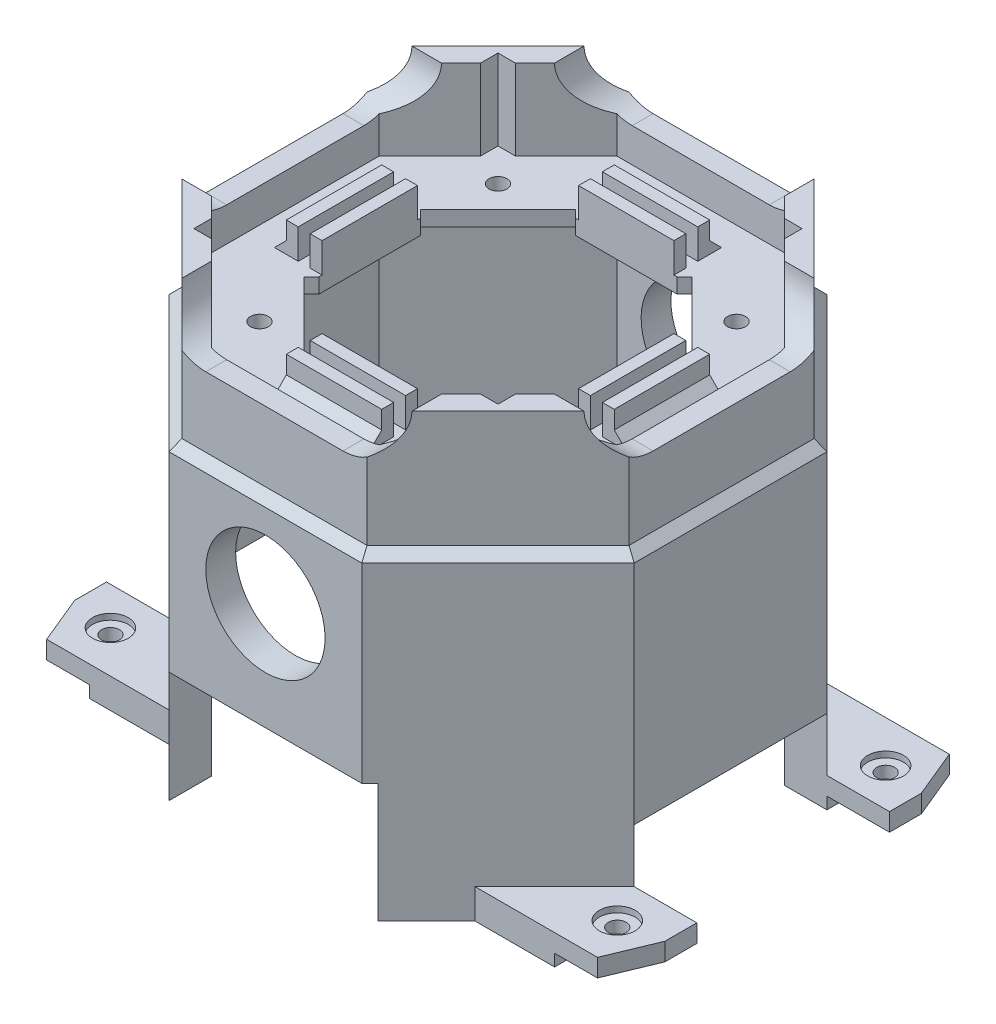
SolidWorks part; units mm, degrees
ref_plane "Front Plane" through (0, 0, 0) normal (0, 0, 1) x (1, 0, 0)
ref_plane "Top Plane" through (0, 0, 0) normal (0, 1, 0) x (1, 0, 0)
ref_plane "Right Plane" through (0, 0, 0) normal (1, 0, 0) x (0, 0, -1)
sketch "Sketch1" plane through (0, 0, 0) normal (0, 1, 0) x (1, 0, 0)
  line L1 (15.533, 37.5) -> (-15.533, 37.5)
  line L2 (-15.533, 37.5) -> (-37.5, 15.533)
  line L3 (-37.5, 15.533) -> (-37.5, -15.533)
  line L4 (-37.5, -15.533) -> (-15.533, -37.5)
  line L5 (-15.533, -37.5) -> (15.533, -37.5)
  line L6 (15.533, -37.5) -> (37.5, -15.533)
  line L7 (37.5, -15.533) -> (37.5, 15.533)
  line L8 (37.5, 15.533) -> (15.533, 37.5)
  circle A0 centre (0, 0) radius 37.5 construction
  dimension "D1" = 75
extrude "Boss-Extrude1" add sketch "Sketch1" along normal blind 40
sketch "Sketch7" plane through (0, 0, 0) normal (0, -1, 0) x (1, 0, 0)
  line L0 (-15.533, 37.5) -> (15.533, 37.5) construction
  line L1 (39, 16.1543) -> (16.1543, 39)
  line L2 (16.1543, 39) -> (-16.1543, 39)
  line L3 (-16.1543, 39) -> (-39, 16.1543)
  line L4 (-39, 16.1543) -> (-39, -16.1543)
  line L5 (-39, -16.1543) -> (-16.1543, -39)
  line L6 (-16.1543, -39) -> (16.1543, -39)
  line L7 (16.1543, -39) -> (39, -16.1543)
  line L8 (39, -16.1543) -> (39, 16.1543)
  circle A0 centre (0, 0) radius 39 construction
  dimension "76" = 78
extrude "Boss-Extrude4" add sketch "Sketch7" along normal blind 55
sketch "Sketch18" plane through (0, 40, 0) normal (0, 1, 0) x (1, 0, 0)
  line L0 (-39, -16.1543) -> (-39, 16.1543) construction
  line L2 (-39, 7.5) -> (-39, -7.5)
  line L12 (-39, 7.5) -> (-33, 7.5)
  line L14 (-33, 7.5) -> (-33, -7.5)
  line L15 (-33, -7.5) -> (-39, -7.5)
  line L16 (0, -55) -> (0, 55) construction
  line L17 (33, 7.5) -> (33, -7.5)
  line L18 (39, 7.5) -> (33, 7.5)
  line L19 (39, 7.5) -> (39, -7.5)
  line L20 (33, -7.5) -> (39, -7.5)
  point P1 (-33, 0)
  dimension "D1" = 15
  dimension "D2" = 6
  dimension "D3" = 6
sketch "Sketch3" plane through (0, 0, 37.5) normal (0, 0, 1) x (1, 0, 0)
  line L0 (-11.5, 18) -> (11.5, 18) construction
  line L1 (-11.5, 25.8) -> (11.5, 25.8)
  line L2 (-11.5, 10.2) -> (11.5, 10.2)
  line L4 (-15.533, 40) -> (15.533, 40) construction
  arc A0 (-11.5, 25.8) -> (-11.5, 10.2) centre (-11.5, 18) ccw
  arc A1 (11.5, 10.2) -> (11.5, 25.8) centre (11.5, 18) ccw
  point P2 (0, 18)
  dimension "D1" = 7.8
  dimension "D2" = 23
  dimension "D3" = 22
extrude "Cut-Extrude1" cut sketch "Sketch3" against normal up to surface (75 mm away) up to face at (0, 20, -37.5)
sketch "Sketch4" plane through (-37.5, 0, 0) normal (-1, 0, 0) x (0, 0, 1)
  line L0 (-11.5, 18) -> (11.5, 18) construction
  line L1 (-11.5, 25.8) -> (11.5, 25.8)
  line L2 (-11.5, 10.2) -> (11.5, 10.2)
  line L4 (-15.533, 40) -> (15.533, 40) construction
  arc A0 (-11.5, 25.8) -> (-11.5, 10.2) centre (-11.5, 18) ccw
  arc A1 (11.5, 10.2) -> (11.5, 25.8) centre (11.5, 18) ccw
  point P2 (0, 18)
  dimension "D1" = 7.8
  dimension "D2" = 22
  dimension "D3" = 23
extrude "Cut-Extrude2" cut sketch "Sketch4" against normal up to surface and the other way up to surface up to face at (39, -27.5, 0) other way up to face at (-39, -27.5, 0)
chamfer "Chamfer5" distance 3 angle 45 8 edges at (-39, 0, 0) (-27.5772, 0, -27.5772) (0, 0, -39) (27.5772, 0, -27.5772) (39, 0, 0) (27.5772, 0, 27.5772) (0, 0, 39) (-27.5772, 0, 27.5772)
shell "Shell1" [suppressed] thickness 2
sketch "Sketch11" plane through (0, 0, -39) normal (0, 0, 1) x (1, 0, 0)
  line L1 (16.1543, -55) -> (-16.1543, -55) construction
  circle A0 centre (0, -17) radius 10
  dimension "D2" = 20
  dimension "D1" = 38
extrude "Cut-Extrude5" cut sketch "Sketch11" along normal up to surface (78 mm away) up to face at (0, -29, 39)
chamfer "Chamfer7" distance 3 angle 45 8 edges at (37.5, 40, 0) (26.5165, 40, 26.5165) (0, 40, 37.5) (-26.5165, 40, 26.5165) (-37.5, 40, 0) (26.5165, 40, -26.5165) (-26.5165, 40, -26.5165) (0, 40, -37.5)
extrude "Boss-Extrude10" add sketch "Sketch18" along normal blind 50 and the other way up to vertex (14.2 mm away) separate body
sketch "Sketch20" plane through (0, 90, 0) normal (0, 1, 0) x (1, 0, 0)
  line L1 (-39, 7.5) -> (39, 7.5)
  line L2 (-39, 7.5) -> (-39, -7.5)
  line L3 (-39, -7.5) -> (39, -7.5)
  line L4 (39, 7.5) -> (39, -7.5)
extrude "Boss-Extrude11" add sketch "Sketch20" along normal blind 6
chamfer "Chamfer8" distance 3 angle 45 2 edges at (-39, 25.8, 0) (39, 25.8, 0)
chamfer "Chamfer9" distance 1 angle 45 13 edges at (-33, 57.9, -7.5) (0, 90, -7.5) (33, 57.9, -7.5) (-33, 57.9, 7.5) (0, 90, 7.5) (33, 57.9, 7.5) (39, 62.4, -7.5) (0, 96, -7.5) (-39, 62.4, -7.5) (-39, 96, 0) (39, 62.4, 7.5) (0, 96, 7.5) (-39, 62.4, 7.5)
sketch "Sketch21" plane through (0, 0, 39) normal (0, 0, 1) x (1, 0, 0)
  line L0 (39, -55) -> (16.1543, -55) construction
  line L1 (-17.5, -35) -> (17.5, -35)
  line L2 (-17.5, -35) -> (-17.5, -55)
  line L3 (-17.5, -55) -> (17.5, -55)
  line L4 (17.5, -35) -> (17.5, -55)
  point P6 (0, -35)
  dimension "D1" = 35
  dimension "D2" = 20
extrude "Cut-Extrude6" cut sketch "Sketch21" against normal up to surface (78 mm away)
sketch "Sketch22" plane through (-39, 0, 0) normal (-1, 0, 0) x (0, 0, 1)
  line L0 (-16.1543, -55) -> (-16.1543, -3) construction
  line L1 (-16.1543, -41) -> (16.1543, -41)
  line L2 (-16.1543, -41) -> (-16.1543, -55)
  line L3 (-16.1543, -55) -> (16.1543, -55)
  line L4 (16.1543, -41) -> (16.1543, -55)
  dimension "D1" = 14
extrude "Cut-Extrude7" cut sketch "Sketch22" against normal up to surface (78 mm away) up to face at (39, -29, 0)
sketch "Sketch23" plane through (0, 96, 0) normal (0, 1, 0) x (1, 0, 0)
  line L0 (39, 16.1543) -> (39, -16.1543) construction
  line L1 (-39, -39) -> (39, -39)
  line L2 (-39, -39) -> (-39, 39)
  line L3 (-39, 39) -> (39, 39)
  line L4 (39, -39) -> (39, 39)
  line L5 (-39, -39) -> (39, 39) construction
  line L6 (-39, 39) -> (39, -39) construction
  line L7 (-16.1543, 39) -> (16.1543, 39) construction
  point P0 (0, 0)
extrude "Cut-Extrude8" [suppressed] cut sketch "Sketch23" against normal up to vertex
sketch "Sketch25" plane through (0, -55, 0) normal (0, -1, 0) x (1, 0, 0)
  line L0 (-39, -16.1543) -> (-49.5, -16.1543)
  line L1 (-42.5, -22.5) -> (42.5, -22.5) construction
  line L2 (-42.5, -22.5) -> (-42.5, 22.5) construction
  line L3 (-42.5, 22.5) -> (42.5, 22.5) construction
  line L4 (42.5, -22.5) -> (42.5, 22.5) construction
  line L5 (-42.5, -22.5) -> (42.5, 22.5) construction
  line L6 (-42.5, 22.5) -> (42.5, -22.5) construction
  line L7 (-49.5, -16.1543) -> (-49.5, -29.5)
  line L8 (-49.5, -29.5) -> (-25.6543, -29.5)
  line L9 (-39, -16.1543) -> (-17.5, -37.6543) construction
  line L12 (-39, -16.1543) -> (-25.6543, -29.5)
  line L13 (55, 0) -> (-55, 0) construction
  line L14 (-39, 16.1543) -> (-49.5, 16.1543)
  line L15 (-49.5, 16.1543) -> (-49.5, 29.5)
  line L16 (-49.5, 29.5) -> (-25.6543, 29.5)
  line L17 (-39, 16.1543) -> (-25.6543, 29.5)
  line L18 (0, -55) -> (0, 55) construction
  line L19 (39, -16.1543) -> (49.5, -16.1543)
  line L20 (49.5, -16.1543) -> (49.5, -29.5)
  line L21 (49.5, -29.5) -> (25.6543, -29.5)
  line L22 (39, -16.1543) -> (25.6543, -29.5)
  line L23 (39, 16.1543) -> (25.6543, 29.5)
  line L24 (49.5, 29.5) -> (25.6543, 29.5)
  line L25 (49.5, 16.1543) -> (49.5, 29.5)
  line L26 (39, 16.1543) -> (49.5, 16.1543)
  circle A0 centre (-42.5, 22.5) radius 1.5
  circle A1 centre (42.5, 22.5) radius 1.5
  circle A2 centre (42.5, -22.5) radius 1.5
  circle A3 centre (-42.5, -22.5) radius 1.5
  point P0 (0, 0)
  dimension "D3" = 3
  dimension "D1" = 85
  dimension "D2" = 45
  dimension "D4" = 7
  dimension "D5" = 7
extrude "Boss-Extrude12" add sketch "Sketch25" against normal blind 5
sketch "Sketch26" plane through (0, 40, 0) normal (0, 1, 0) x (1, 0, 0)
  line L1 (-14.2904, 34.5) -> (14.2904, 34.5)
  line L2 (-14.2904, 34.5) -> (-14.2904, -34.5)
  line L3 (-14.2904, -34.5) -> (14.2904, -34.5)
  line L4 (14.2904, 34.5) -> (14.2904, -34.5)
extrude "Cut-Extrude9" cut sketch "Sketch26" against normal blind 15
sketch "Sketch27" plane through (0, 40, 0) normal (0, 1, 0) x (1, 0, 0)
  line L1 (34.5, 7.5) -> (-34.5, 7.5)
  line L2 (34.5, 7.5) -> (34.5, -7.5)
  line L3 (34.5, -7.5) -> (-34.5, -7.5)
  line L4 (-34.5, 7.5) -> (-34.5, -7.5)
  line L5 (-34.5, 14.2904) -> (-34.5, -14.2904) construction
  line L6 (34.5, -14.2904) -> (34.5, 14.2904) construction
  line L7 (14.2904, -34.5) -> (14.2904, 34.5) construction
  point P10 (14.2904, 0)
  point P11 (34.5, 0)
  dimension "D1" = 15
extrude "Cut-Extrude10" cut sketch "Sketch27" against normal blind 15
chamfer "Chamfer10" distance 8 angle 22.5 4 edges at (49.5, -52.5, 29.5) (49.5, -52.5, -29.5) (-49.5, -52.5, -29.5) (-49.5, -52.5, 29.5)
sketch "Sketch28" plane through (0, -55, 0) normal (0, -1, 0) x (1, 0, 0)
  line L0 (46.1863, 29.5) -> (25.6543, 29.5) construction
  line L1 (39, 29.5) -> (49.5, 29.5)
  line L2 (39, 29.5) -> (39, -29.5)
  line L3 (39, -29.5) -> (49.5, -29.5)
  line L4 (49.5, 29.5) -> (49.5, -29.5)
  line L5 (25.6543, -29.5) -> (46.1863, -29.5) construction
  line L6 (39, -16.1543) -> (39, 16.1543) construction
  line L7 (49.5, 16.1543) -> (49.5, 21.5) construction
  line L8 (0, -42.9) -> (0, 42.9) construction
  line L9 (-39, -29.5) -> (-49.5, -29.5)
  line L10 (-49.5, 29.5) -> (-49.5, -29.5)
  line L11 (-39, 29.5) -> (-49.5, 29.5)
  line L12 (-39, 29.5) -> (-39, -29.5)
extrude "Cut-Extrude11" cut sketch "Sketch28" against normal blind 2
sketch "Sketch35" plane through (0, 96, 0) normal (0, 1, 0) x (1, 0, 0)
  line L0 (39, 16.1543) -> (39, -16.1543) construction
  line L1 (-39, -39) -> (39, -39)
  line L2 (-39, -39) -> (-39, 39)
  line L3 (-39, 39) -> (39, 39)
  line L4 (39, -39) -> (39, 39)
  line L5 (-39, -16.1543) -> (-39, 16.1543) construction
  line L6 (-16.1543, 39) -> (16.1543, 39) construction
  line L7 (16.1543, -39) -> (-16.1543, -39) construction
extrude "Cut-Extrude18" cut sketch "Sketch35" against normal blind 78
sketch "Sketch29" plane through (0, -50, 0) normal (0, 1, 0) x (1, 0, 0)
  circle A0 centre (-42.5, 22.5) radius 3
  circle A1 centre (42.5, 22.5) radius 3
  circle A2 centre (42.5, -22.5) radius 3
  circle A3 centre (-42.5, -22.5) radius 3
  dimension "D1" = 6
extrude "Cut-Extrude12" cut sketch "Sketch29" against normal blind 1
sketch "Sketch39" plane through (0, 0, 0) normal (0, 1, 0) x (-1, 0, 0)
  line L0 (-34, 14.0833) -> (-14.0833, 34)
  line L1 (-14.0833, 34) -> (14.0833, 34)
  line L2 (14.0833, 34) -> (34, 14.0833)
  line L3 (34, 14.0833) -> (34, -14.0833)
  line L4 (34, -14.0833) -> (14.0833, -34)
  line L5 (14.0833, -34) -> (-14.0833, -34)
  line L6 (-14.0833, -34) -> (-34, -14.0833)
  line L7 (-34, -14.0833) -> (-34, 14.0833)
  line L9 (34, 0) -> (-34, 0) construction
  line L13 (0, 34) -> (0, -34) construction
  dimension "D1" = 68
  dimension "D2" = 68
  dimension "D3" = 68
  dimension "D4" = 34
extrude "Cut-Extrude19" cut sketch "Sketch39" along normal up to surface (73 mm away) from surface
sketch "Sketch47" plane through (0, -55, 0) normal (0, -1, 0) x (1, 0, 0)
  line L1 (9.5269, 23) -> (-9.5269, 23)
  line L2 (-9.5269, 23) -> (-23, 9.5269)
  line L3 (-23, 9.5269) -> (-23, -9.5269)
  line L4 (-23, -9.5269) -> (-9.5269, -23)
  line L5 (-9.5269, -23) -> (9.5269, -23)
  line L6 (9.5269, -23) -> (23, -9.5269)
  line L7 (23, -9.5269) -> (23, 9.5269)
  line L8 (23, 9.5269) -> (9.5269, 23)
  line L9 (-14.0833, 34) -> (14.0833, 34) construction
  line L11 (14.0833, 34) -> (-14.0833, 34)
  line L12 (-14.0833, 34) -> (-34, 14.0833)
  line L13 (-34, 14.0833) -> (-34, -14.0833)
  line L14 (-34, -14.0833) -> (-14.0833, -34)
  line L15 (-14.0833, -34) -> (14.0833, -34)
  line L16 (14.0833, -34) -> (34, -14.0833)
  line L17 (34, -14.0833) -> (34, 14.0833)
  line L18 (34, 14.0833) -> (14.0833, 34)
  circle A0 centre (0, 0) radius 23 construction
  circle A1 centre (0, 0) radius 34 construction
  dimension "D1" = 11
extrude "Boss-Extrude16" add sketch "Sketch47" against normal blind 2.5 from offset 57 offset against normal yes
chamfer "Chamfer13" distance 10 angle 45 4 edges at (-34, 2, 0) (0, 2, -34) (34, 2, 0) (0, 2, 34)
sketch "Sketch48" plane through (0, 2, 0) normal (0, -1, 0) x (1, 0, 0)
  line L1 (-20, -20) -> (20, -20) construction
  line L2 (-20, -20) -> (-20, 20) construction
  line L3 (-20, 20) -> (20, 20) construction
  line L4 (20, -20) -> (20, 20) construction
  line L5 (-20, -20) -> (20, 20) construction
  line L6 (-20, 20) -> (20, -20) construction
  circle A0 centre (-20, 20) radius 1.5
  circle A1 centre (20, 20) radius 1.5
  circle A2 centre (20, -20) radius 1.5
  circle A3 centre (-20, -20) radius 1.5
  point P0 (0, 0)
  dimension "D1" = 3
  dimension "D2" = 40
extrude "Cut-Extrude22" cut sketch "Sketch48" against normal up to surface (2.5 mm away) up to face at (0, 4.5, 0)
sketch "Sketch49" plane through (0, 4.5, 0) normal (0, 1, 0) x (1, 0, 0)
  line L1 (-25.5, -25.5) -> (25.5, -25.5)
  line L2 (-25.5, -25.5) -> (-25.5, 25.5)
  line L3 (-25.5, 25.5) -> (25.5, 25.5)
  line L4 (25.5, -25.5) -> (25.5, 25.5)
  line L5 (-25.5, -25.5) -> (25.5, 25.5) construction
  line L6 (-25.5, 25.5) -> (25.5, -25.5) construction
  point P0 (0, 0)
  dimension "D1" = 51
extrude "Cut-Extrude23" cut sketch "Sketch49" along normal up to surface (13.5 mm away) up to face at (-25.2791, 18, -25.2791)
sketch "Sketch51" plane through (0, 2, 0) normal (0, 1, 0) x (1, 0, 0)
  line L0 (25.5, 8) -> (27.5, 8)
  line L1 (-25.5, -25.5) -> (25.5, -25.5) construction
  line L2 (-25.5, -25.5) -> (-25.5, 25.5) construction
  line L3 (-25.5, 25.5) -> (25.5, 25.5) construction
  line L4 (25.5, -25.5) -> (25.5, 25.5) construction
  line L5 (-25.5, -25.5) -> (25.5, 25.5) construction
  line L6 (-25.5, 25.5) -> (25.5, -25.5) construction
  line L7 (-8, 25.5) -> (8, 25.5)
  line L8 (-8, 25.5) -> (-8, 27.5)
  line L9 (-8, 27.5) -> (8, 27.5)
  line L10 (8, 25.5) -> (8, 27.5)
  line L11 (-8, 23.5) -> (8, 23.5)
  line L12 (-8, 23.5) -> (-8, 21.5)
  line L13 (-8, 21.5) -> (8, 21.5)
  line L14 (8, 23.5) -> (8, 21.5)
  line L15 (25.5, 8) -> (25.5, -8)
  line L16 (25.5, -8) -> (27.5, -8)
  line L17 (27.5, 8) -> (27.5, -8)
  line L18 (23.5, 8) -> (21.5, 8)
  line L19 (23.5, 8) -> (23.5, -8)
  line L20 (23.5, -8) -> (21.5, -8)
  line L21 (21.5, 8) -> (21.5, -8)
  line L22 (8, -25.5) -> (8, -27.5)
  line L23 (8, -25.5) -> (-8, -25.5)
  line L24 (-8, -25.5) -> (-8, -27.5)
  line L25 (8, -27.5) -> (-8, -27.5)
  line L26 (8, -23.5) -> (8, -21.5)
  line L27 (8, -23.5) -> (-8, -23.5)
  line L28 (-8, -23.5) -> (-8, -21.5)
  line L29 (8, -21.5) -> (-8, -21.5)
  line L30 (-25.5, -8) -> (-27.5, -8)
  line L31 (-25.5, -8) -> (-25.5, 8)
  line L32 (-25.5, 8) -> (-27.5, 8)
  line L33 (-27.5, -8) -> (-27.5, 8)
  line L34 (-23.5, -8) -> (-21.5, -8)
  line L35 (-23.5, -8) -> (-23.5, 8)
  line L36 (-23.5, 8) -> (-21.5, 8)
  line L37 (-21.5, -8) -> (-21.5, 8)
  point P0 (0, 0)
  point P14 (0, 27.5)
  point P15 (0, 21.5)
  point P16 (0, 0)
  point P17 (0, 0)
  point P43 (0, 0)
  dimension "D1" = 51
  dimension "D2" = 16
  dimension "D3" = 2
  dimension "D4" = 2
  dimension "D5" = 4
extrude "Boss-Extrude17" add sketch "Sketch51" along normal blind 7.5
chamfer "Chamfer14" distance 2 angle 45 8 edges at (-23, 3.25, -8) (23, 3.25, -8) (23, 3.25, 8) (8, 3.25, -23) (-8, 3.25, -23) (-23, 3.25, 8) (-8, 3.25, 23) (8, 3.25, 23)
chamfer "Chamfer15" distance 2 angle 45 4 edges at (0, 4.5, -27.5) (27.5, 4.5, 0) (0, 4.5, 27.5) (-27.5, 4.5, 0)
